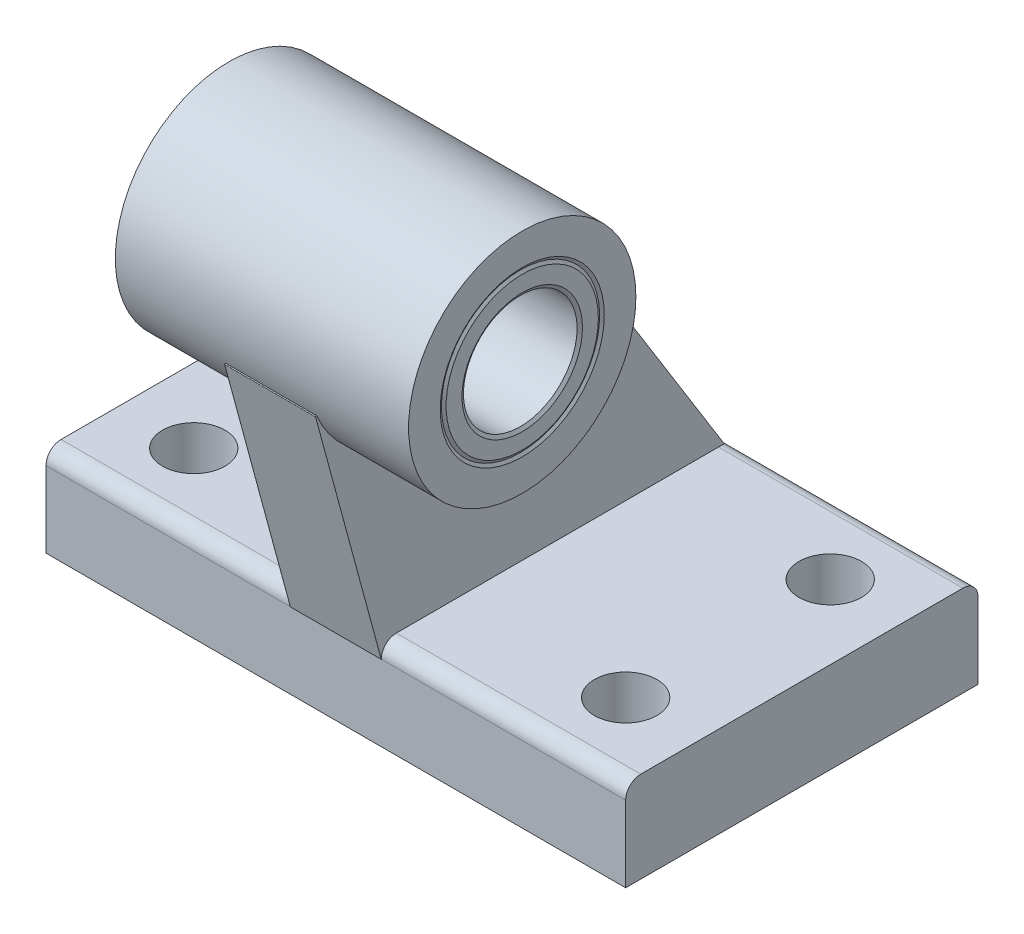
SolidWorks part; units mm, degrees
ref_plane "Front Plane" through (0, 0, 0) normal (0, 0, 1) x (1, 0, 0)
ref_plane "Top Plane" through (0, 0, 0) normal (0, 1, 0) x (1, 0, 0)
ref_plane "Right Plane" through (0, 0, 0) normal (1, 0, 0) x (0, 0, -1)
ref_plane "Plane1" through (0, 0, 0) normal (1, 0, 0) x (0, 0, -1)
sketch "Sketch1" plane through (0, 0, 0) normal (1, 0, 0) x (0, 0, -1)
  line L0 (-15.5, 6.672) -> (-15.5, 0)
  line L1 (-15.5, 0) -> (15.5, 0)
  line L2 (15.5, 0) -> (15.5, 6.672)
  line L3 (14.172, 8) -> (-14.172, 8)
  arc A0 (15.5, 6.672) -> (14.172, 8) centre (14.172, 6.672) ccw
  arc A1 (-14.172, 8) -> (-15.5, 6.672) centre (-14.172, 6.672) ccw
extrude "Boss-Extrude1" add sketch "Sketch1" against normal blind 25.5 and the other way blind 25.5
ref_plane "Plane2" through (0, 0, 0) normal (1, 0, 0) x (0, 0, -1)
sketch "Sketch2" plane through (0, 0, 0) normal (1, 0, 0) x (0, 0, -1)
  line L0 (-21.2832, 28.0222) -> (-15.5, 6.656)
  line L1 (-14.156, 8) -> (14.6753, 8)
  line L2 (14.6753, 8) -> (-2.7587, 36.0741)
  arc A0 (-21.189, 28.055) -> (-21.2832, 28.0222) centre (-21.2349, 28.0353) ccw
  arc A1 (-15.5, 6.656) -> (-14.156, 8) centre (-14.156, 6.656) cw
  arc A2 (-2.7587, 36.0741) -> (-2.8469, 36.0276) centre (-2.8012, 36.0477) ccw
  arc A3 (-2.8469, 36.0276) -> (-21.189, 28.055) centre (-12, 32) cw
extrude "Boss-Extrude2" add sketch "Sketch2" against normal blind 4 and the other way blind 4
ref_plane "Plane3" through (0, 0, 0) normal (1, 0, 0) x (0, 0, -1)
sketch "Sketch3" plane through (0, 0, 0) normal (1, 0, 0) x (0, 0, -1)
  circle A0 centre (-12, 32) radius 10
extrude "Boss-Extrude3" add sketch "Sketch3" against normal blind 12.9 and the other way blind 12.9
ref_plane "Plane4" through (0, 0, 9) normal (0, 0, 1) x (1, 0, 0)
sketch "Sketch4" plane through (0, 0, 9) normal (0, 0, 1) x (1, 0, 0)
  line L0 (-19, 0) -> (-21.75, 0)
  line L1 (-21.75, 0) -> (-21.75, 8)
  line L2 (-21.75, 8) -> (-19, 8)
  line L3 (-19, 8) -> (-19, 0)
  line L4 (-19, 8) -> (-19, 0) construction
revolve "Cut-Revolve1" cut sketch "Sketch4" angle 360 about L4
ref_plane "Plane5" through (0, 0, 9) normal (0, 0, 1) x (1, 0, 0)
sketch "Sketch5" plane through (0, 0, 9) normal (0, 0, 1) x (1, 0, 0)
  line L0 (19, 0) -> (16.25, 0)
  line L1 (16.25, 0) -> (16.25, 8)
  line L2 (16.25, 8) -> (19, 8)
  line L3 (19, 8) -> (19, 0)
  line L4 (19, 8) -> (19, 0) construction
revolve "Cut-Revolve2" cut sketch "Sketch5" angle 360 about L4
ref_plane "Plane6" through (0, 0, -9) normal (0, 0, 1) x (1, 0, 0)
sketch "Sketch6" plane through (0, 0, -9) normal (0, 0, 1) x (1, 0, 0)
  line L0 (-19, 0) -> (-21.75, 0)
  line L1 (-21.75, 0) -> (-21.75, 8)
  line L2 (-21.75, 8) -> (-19, 8)
  line L3 (-19, 8) -> (-19, 0)
  line L4 (-19, 8) -> (-19, 0) construction
revolve "Cut-Revolve3" cut sketch "Sketch6" angle 360 about L4
ref_plane "Plane7" through (0, 0, -9) normal (0, 0, 1) x (1, 0, 0)
sketch "Sketch7" plane through (0, 0, -9) normal (0, 0, 1) x (1, 0, 0)
  line L0 (19, 0) -> (16.25, 0)
  line L1 (16.25, 0) -> (16.25, 8)
  line L2 (16.25, 8) -> (19, 8)
  line L3 (19, 8) -> (19, 0)
  line L4 (19, 8) -> (19, 0) construction
revolve "Cut-Revolve4" cut sketch "Sketch7" angle 360 about L4
ref_plane "Plane8" through (0, 0, 12) normal (0, 0, 1) x (1, 0, 0)
sketch "Sketch8" plane through (0, 0, 12) normal (0, 0, 1) x (1, 0, 0)
  line L0 (-12.9, 32) -> (-12.9, 39.22)
  line L1 (-12.9, 39.22) -> (-12.6113, 38.72)
  line L2 (-12.6113, 38.72) -> (12.6113, 38.72)
  line L3 (12.6113, 38.72) -> (12.9, 39.22)
  line L4 (12.9, 39.22) -> (12.9, 32)
  line L5 (12.9, 32) -> (-12.9, 32)
  line L6 (12.9, 32) -> (-12.9, 32) construction
revolve "Cut-Revolve5" cut sketch "Sketch8" angle 360 about L6
ref_plane "Plane9" through (0, 0, 12) normal (0, 0, 1) x (1, 0, 0)
sketch "Sketch9" plane through (0, 0, 12) normal (0, 0, 1) x (1, 0, 0)
  line L0 (-12.9, 37.3) -> (-12.7268, 37)
  line L1 (-12.7268, 37) -> (12.7268, 37)
  line L2 (12.7268, 37) -> (12.9, 37.3)
  line L3 (12.9, 37.3) -> (12.9, 38.7)
  line L4 (12.9, 38.7) -> (12.7268, 39)
  line L5 (12.7268, 39) -> (-12.7268, 39)
  line L6 (-12.7268, 39) -> (-12.9, 38.7)
  line L7 (-12.9, 38.7) -> (-12.9, 37.3)
  line L8 (12.9, 32) -> (-12.9, 32) construction
revolve "Revolve1" add sketch "Sketch9" angle 360 about L8
